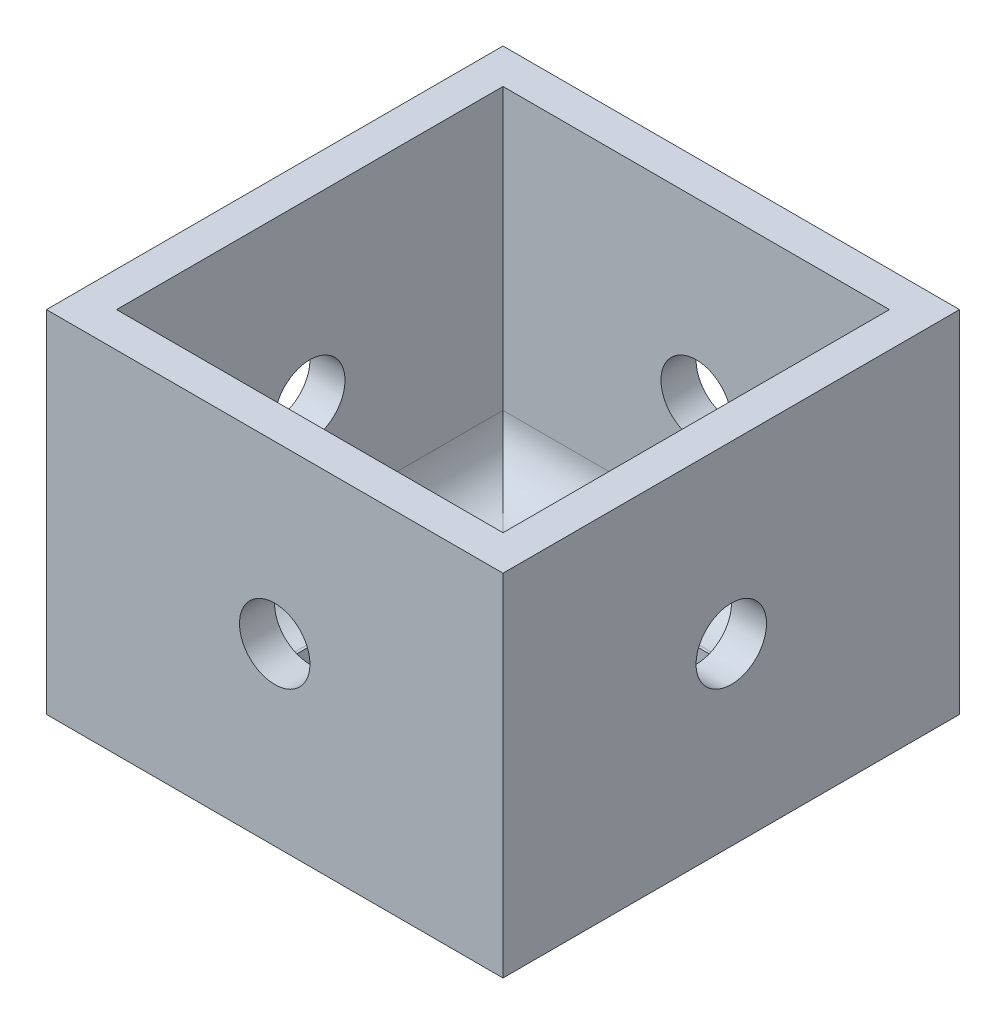
SolidWorks part; units mm, degrees
ref_plane "Front Plane" through (0, 0, 0) normal (0, 0, 1) x (1, 0, 0)
ref_plane "Top Plane" through (0, 0, 0) normal (0, 1, 0) x (1, 0, 0)
ref_plane "Right Plane" through (0, 0, 0) normal (1, 0, 0) x (0, 0, -1)
sketch "Sketch1" plane through (0, 0, 0) normal (0, 1, 0) x (1, 0, 0)
  line L0 (0, 14) -> (28, 14) construction
  line L1 (0, 0) -> (28, 0)
  line L2 (0, 0) -> (0, 28)
  line L3 (0, 28) -> (28, 28)
  line L4 (28, 0) -> (28, 28)
  line L5 (14, 0) -> (14, 28) construction
  line L7 (4, 4) -> (24, 4)
  line L8 (4, 4) -> (4, 24)
  line L9 (4, 24) -> (24, 24)
  line L10 (24, 4) -> (24, 24)
  point P13 (14, 4)
  point P14 (4, 14)
  dimension "D1" = 28
  dimension "D2" = 28
  dimension "D3" = 20
  dimension "D4" = 20
extrude "Extrude-Thin1" add sketch "Sketch1" along normal blind 25.4 thin contours L1 L4 L3 L2 thin type one direction wall 2.54
ref_plane "Plane1" through (0, 0, -14) normal (0, 0, 1) x (1, 0, 0)
ref_plane "Plane2" through (14, 0, 0) normal (1, 0, 0) x (0, 0, -1)
ref_axis "Axis1" through (14, -1.27, -14) along (0, 1, 0)
sketch "Sketch7" plane through (0, 0, 2.54) normal (0, 0, 1) x (1, 0, 0)
  line L0 (14, 25.4) -> (14, 0) construction
  line L1 (-2.54, 25.4) -> (30.54, 25.4) construction
  line L2 (-2.54, 0) -> (30.54, 0) construction
hole_wizard "Tap Drill for 1/4-20 Tap2" positions "Sketch8" profile "Sketch9" hole size "1/4-20" standard "ANSI Inch"
sketch "Sketch8" plane through (0, 0, 2.54) normal (0, 0, 1) x (1, 0, 0)
  line L0 (14, 25.4) -> (14, 0) construction
  point P0 (14, 12.7)
sketch "Sketch9" plane through (14, 12.7, 2.54) normal (1, 0, 0) x (0, -1, 0)
  line L0 (0, 0) -> (0, 9.1538)
  line L1 (0, 9.1538) -> (2.5527, 7.62)
  line L2 (2.5527, 7.62) -> (2.5527, 0)
  line L5 (2.5527, 0) -> (0, 0)
  line L10 (0, 9.1538) -> (-2.5527, 7.62) construction
  line L11 (0, -6.35) -> (0, 107.95) construction
  dimension "Hole Dia." = 5.1054
  dimension "Hole Depth" = 7.62
  dimension "Drill Angle" = 118
pattern_circular "CirPattern1" count 4 over 360 about axis through (14, -1.27, -14) along (0, 1, 0) of "Tap Drill for 1/4-20 Tap2"
extrude "Boss-Extrude1" add sketch "Sketch1<3>" along normal blind 1.27
sketch "Sketch1<3>" plane through (0, 0, 0) normal (0, 1, 0) x (1, 0, 0) same geometry as "Sketch1"
fillet "Fillet1" radius 3.81 4 edges at (14, 1.27, -28) (0, 1.27, -14) (14, 1.27, 0) (28, 1.27, -14)
